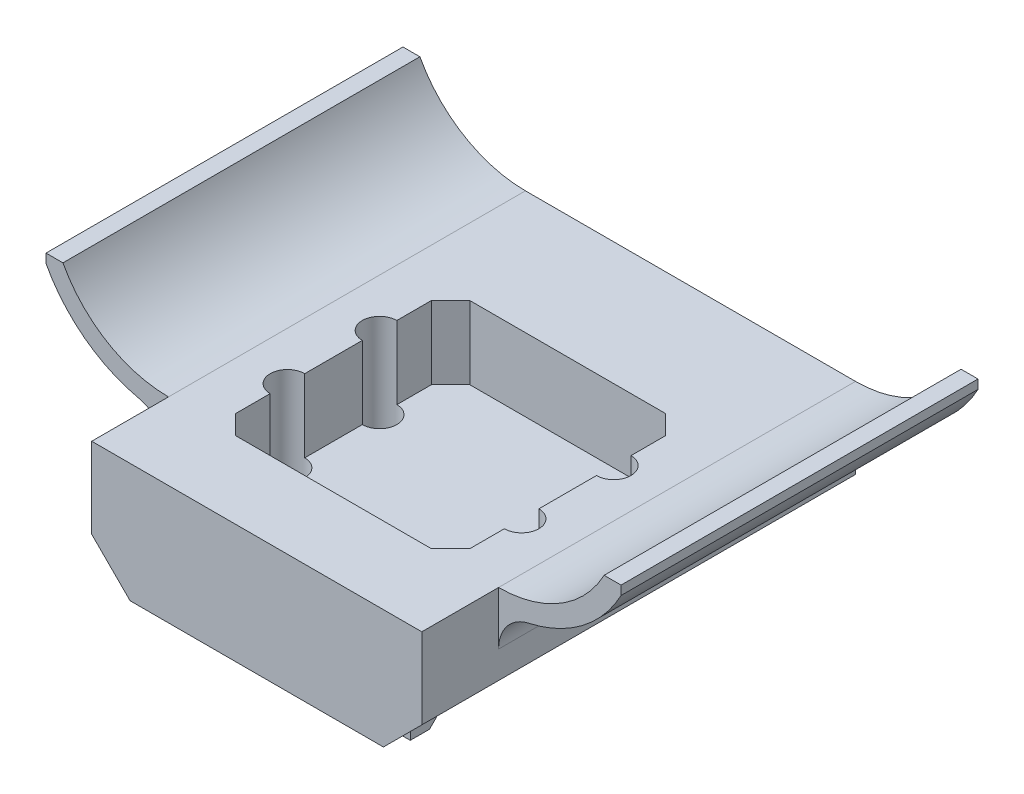
SolidWorks part; units mm, degrees
ref_plane "Plan de face" through (0, 0, 0) normal (0, 0, 1) x (1, 0, 0)
ref_plane "Plan de dessus" through (0, 0, 0) normal (0, 1, 0) x (1, 0, 0)
ref_plane "Plan de droite" through (0, 0, 0) normal (1, 0, 0) x (0, 0, -1)
sketch "Esquisse1" plane through (0, 0, 0) normal (0, 1, 0) x (1, 0, 0)
  line L1 (-8.6, 0) -> (8.6, 0)
  line L2 (-8.6, 0) -> (-8.6, 22.6)
  line L3 (-8.6, 22.6) -> (8.6, 22.6)
  line L4 (8.6, 0) -> (8.6, 22.6)
  dimension "D1" = 17.2
  dimension "D2" = 22.6
extrude "Boss.-Extru.1" add sketch "Esquisse1" along normal blind 6.2
sketch "Esquisse2" plane through (0, 6.2, 0) normal (0, 1, 0) x (1, 0, 0)
  line L0 (0, 0) -> (0, 10.1) construction
  line L1 (-5.1, 4) -> (5.1, 4)
  line L2 (-6.1, 5) -> (-6.1, 6.8)
  line L3 (-5.1, 16.2) -> (5.1, 16.2)
  line L4 (6.1, 5) -> (6.1, 6.8)
  line L5 (-6.1, 4) -> (6.1, 16.2) construction
  line L6 (-6.1, 16.2) -> (6.1, 4) construction
  line L8 (-6.1, 15.2) -> (-5.1, 16.2)
  line L9 (5.1, 16.2) -> (6.1, 15.2)
  line L10 (5.1, 4) -> (6.1, 5)
  line L11 (-6.1, 5) -> (-5.1, 4)
  line L12 (-6.1, 13.4) -> (-6.1, 15.2)
  line L13 (-6.1, 8.6) -> (-6.1, 11.6)
  line L14 (6.1, 13.4) -> (6.1, 15.2)
  line L15 (6.1, 8.6) -> (6.1, 11.6)
  line L29 (-8.6, 0) -> (8.6, 0) construction
  arc A0 (-6.1, 13.4) -> (-6.1, 11.6) centre (-6.1, 12.5) ccw
  arc A1 (-6.1, 8.6) -> (-6.1, 6.8) centre (-6.1, 7.7) ccw
  arc A2 (6.1, 11.6) -> (6.1, 13.4) centre (6.1, 12.5) ccw
  arc A3 (6.1, 6.8) -> (6.1, 8.6) centre (6.1, 7.7) ccw
  point P0 (0, 10.1)
  dimension "D3" = 1.8
  dimension "D1" = 12.2
  dimension "D2" = 4
  dimension "D4" = 3.7
  dimension "D9" = 3.7
  dimension "D10" = 12.2
extrude "Enlèv. mat.-Extru.1" cut sketch "Esquisse2" against normal blind 3.8
sketch "Esquisse3" plane through (0, 2.4, 0) normal (0, 1, 0) x (1, 0, 0)
  circle A0 centre (6.1, 12.5) radius 0.9
  circle A1 centre (-6.1, 12.5) radius 0.9
  circle A2 centre (-6.1, 7.7) radius 0.9
  circle A3 centre (6.1, 7.7) radius 0.9
extrude "Enlèv. mat.-Extru.2" cut sketch "Esquisse3" against normal through all
chamfer "Chanfrein1" distance 2 angle 45 3 edges at (-8.6, 0, -11.3) (8.6, 0, -11.3) (0, 0, -22.6)
sketch "Esquisse4" plane through (0, 0, -22.6) normal (0, 0, -1) x (-1, 0, 0)
  line L0 (-8.6, 6.2) -> (8.6, 6.2) construction
  line L1 (-8.6, 6.2) -> (-8.6, 5.2)
  line L2 (-14.9824, 9.0294) -> (-14.9824, 9.5)
  line L3 (-14.9824, 9.5) -> (-14.1, 9.5)
  arc A0 (-8.6, 6.2) -> (-14.1, 9.5) centre (-8.6, 12.4333) cw
  arc A1 (-8.6, 5.2) -> (-14.9824, 9.0294) centre (-8.6, 12.4333) cw
  dimension "D1" = 3.3
  dimension "D2" = 5.5
  dimension "D3" = 1
extrude "Boss.-Extru.2" add sketch "Esquisse4" against normal offset from surface (18.6 mm away) 4 up to face at (0, 2.7333, 0)
mirror "Symétrie1" about plane through (0, 0, 0) normal (1, 0, 0) of "Boss.-Extru.2"
sketch "Esquisse5" plane through (0, 0, 0) normal (1, 0, 0) x (0, 0, -1)
  line L0 (4, 0) -> (8, 0)
  line L2 (4, -3) -> (4, 0)
  line L3 (4, -3) -> (5, -3)
  line L4 (5, -3) -> (8, 0)
  dimension "D1" = 4
  dimension "D2" = 3
  dimension "D3" = 1
  dimension "D4" = 4
extrude "Boss.-Extru.3" add sketch "Esquisse5" along normal mid plane 8
fillet "Congé1" radius 2 3 edges at (0, 0, -8) (-8.6, 5.2, -13.3) (8.6, 5.2, -13.3)
